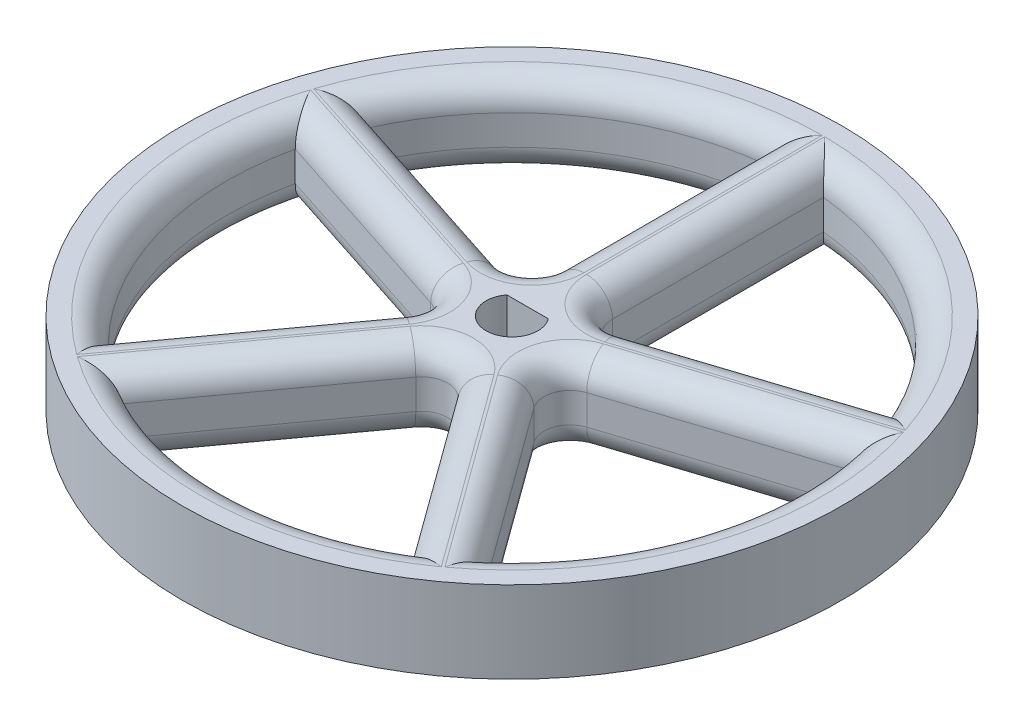
SolidWorks part; units mm, degrees
ref_plane "정면" through (0, 0, 0) normal (0, 0, 1) x (1, 0, 0)
ref_plane "윗면" through (0, 0, 0) normal (0, 1, 0) x (1, 0, 0)
ref_plane "우측면" through (0, 0, 0) normal (1, 0, 0) x (0, 0, -1)
sketch "Sketch4" plane through (0, 0, 0) normal (0, 1, 0) x (1, 0, 0)
  line L0 (-0.6743, 1.2) -> (-2.2743, 1.2)
  line L1 (-0.6743, 1.2) -> (0.9257, 1.2)
  line L2 (-2.7734, 5.6419) -> (-2.7734, 21.8996)
  line L3 (1.4248, 5.6419) -> (1.4248, 21.8996)
  line L4 (4.0428, 3.7398) -> (19.5048, 8.7637)
  line L5 (5.3402, -0.2529) -> (20.8021, 4.771)
  line L6 (4.3402, -3.3306) -> (13.8962, -16.4833)
  line L7 (0.9437, -5.7982) -> (10.4998, -18.951)
  line L8 (-2.2923, -5.7982) -> (-11.8484, -18.951)
  line L9 (-5.6888, -3.3306) -> (-15.2448, -16.4833)
  line L10 (-5.3914, 3.7398) -> (-20.8534, 8.7637)
  line L11 (-6.6888, -0.2529) -> (-22.1508, 4.771)
  circle A0 centre (-0.6743, 0) radius 25.4
  arc A1 (-2.2743, 1.2) -> (0.9257, 1.2) centre (-0.6743, 0) ccw
  arc A2 (-2.7734, 21.8996) -> (-20.8534, 8.7637) centre (-0.6743, 0) ccw
  arc A3 (-2.7734, 5.6419) -> (-5.3914, 3.7398) centre (-4.7734, 5.6419) cw
  arc A4 (-22.1508, 4.771) -> (-15.2448, -16.4833) centre (-0.6743, 0) ccw
  arc A5 (-11.8484, -18.951) -> (10.4998, -18.951) centre (-0.6743, 0) ccw
  arc A6 (13.8962, -16.4833) -> (20.8021, 4.771) centre (-0.6743, 0) ccw
  arc A7 (19.5048, 8.7637) -> (1.4248, 21.8996) centre (-0.6743, 0) ccw
  arc A8 (-6.6888, -0.2529) -> (-5.6888, -3.3306) centre (-7.3068, -2.155) cw
  arc A9 (-2.2923, -5.7982) -> (0.9437, -5.7982) centre (-0.6743, -6.9738) cw
  arc A10 (4.3402, -3.3306) -> (5.3402, -0.2529) centre (5.9582, -2.155) cw
  arc A11 (4.0428, 3.7398) -> (1.4248, 5.6419) centre (3.4248, 5.6419) cw
  dimension "D1" = 2
  dimension "D2" = 2
extrude "Boss-Extrude4" add sketch "Sketch4" along normal blind 6.3
fillet "Fillet6" radius 2 20 edges at (-0.6743, 6.3, 22) (5.7217, 6.3, 12.3746) (-0.6743, 6.3, 4.9738) (-7.0704, 6.3, 12.3746) (-21.5976, 6.3, 6.7984) (-10.4668, 6.3, 9.907) (-5.4047, 6.3, 1.537) (-14.4198, 6.3, -2.259) (-13.6056, 6.3, -17.7984) (-3.5978, 6.3, -4.0239) (-2.7734, 6.3, -13.7708) (2.2492, 6.3, -4.0239) (11.7738, 6.3, -6.2518) (12.257, 6.3, -17.7984) (1.4248, 6.3, -13.7708) (4.0561, 6.3, 1.537) (9.1182, 6.3, 9.907) (20.2489, 6.3, 6.7984) (13.0711, 6.3, -2.259) (-13.1224, 6.3, -6.2518)
fillet "Fillet7" radius 2 20 edges at (5.7217, 0, 12.3746) (-0.6743, 0, 22) (-7.0704, 0, 12.3746) (-0.6743, 0, 4.9738) (-10.4668, 0, 9.907) (-21.5976, 0, 6.7984) (-14.4198, 0, -2.259) (-5.4047, 0, 1.537) (-13.1224, 0, -6.2518) (-13.6056, 0, -17.7984) (-2.7734, 0, -13.7708) (-3.5978, 0, -4.0239) (11.7738, 0, -6.2518) (2.2492, 0, -4.0239) (1.4248, 0, -13.7708) (12.257, 0, -17.7984) (9.1182, 0, 9.907) (4.0561, 0, 1.537) (13.0711, 0, -2.259) (20.2489, 0, 6.7984)
